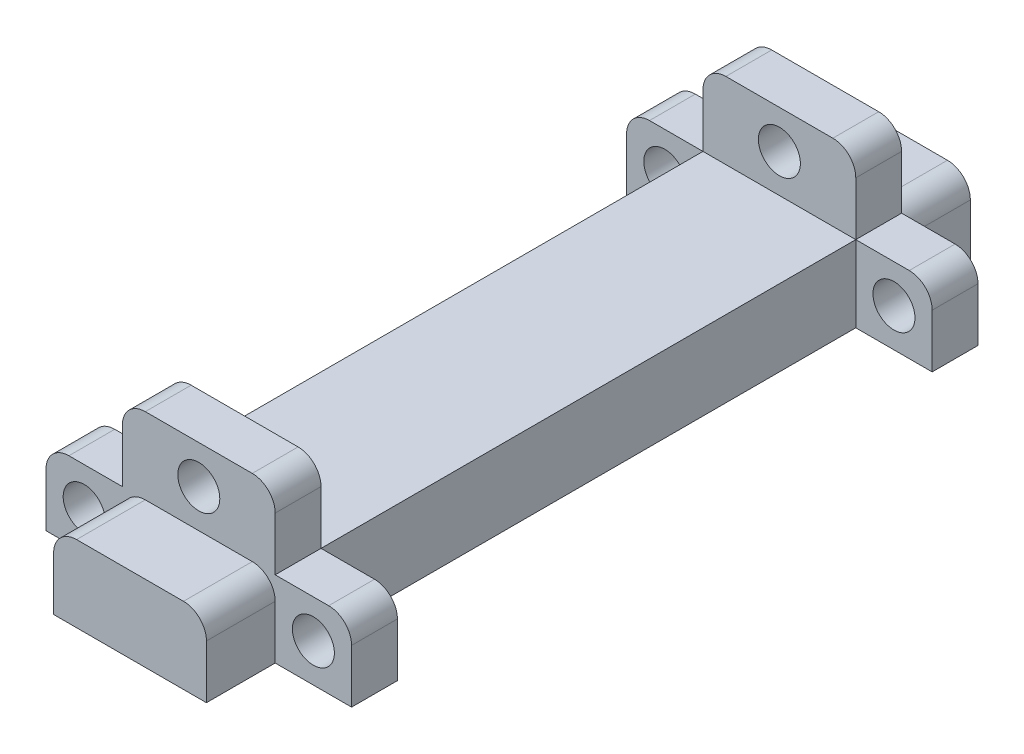
SolidWorks part; units mm, degrees
ref_plane "前视基准面" through (0, 0, 0) normal (0, 0, 1) x (1, 0, 0)
ref_plane "上视基准面" through (0, 0, 0) normal (0, 1, 0) x (1, 0, 0)
ref_plane "右视基准面" through (0, 0, 0) normal (1, 0, 0) x (0, 0, -1)
other "Configuration Table"
sketch "草图1" plane through (0, 0, 0) normal (0, 0, 1) x (1, 0, 0)
  line L1 (0, 0) -> (20, 0)
  line L2 (0, 0) -> (0, 10)
  line L3 (0, 10) -> (20, 10)
  line L4 (20, 0) -> (20, 10)
  dimension "D1" = 20
  dimension "D2" = 10
extrude "凸台-拉伸1" add sketch "草图1" along normal blind 100 contours L2 L3 L4 L1
sketch "草图2" plane through (0, 0, 0) normal (0, 0, -1) x (-1, 0, 0)
  line L1 (-20, 10) -> (0, 10)
  line L2 (-20, 10) -> (-20, 20)
  line L3 (-20, 20) -> (0, 20)
  line L4 (0, 10) -> (0, 20)
  line L5 (0, 0) -> (10, 0)
  line L6 (0, 0) -> (0, 10)
  line L7 (0, 10) -> (10, 10)
  line L8 (10, 0) -> (10, 10)
  line L9 (-20, 0) -> (-30, 0)
  line L10 (-20, 0) -> (-20, 10)
  line L11 (-20, 10) -> (-30, 10)
  line L12 (-30, 0) -> (-30, 10)
  line M12 (0, 10) -> (-20, 10)
  line M13 (-20, 10) -> (-20, 0)
  dimension "D1" = 10
  dimension "D2" = 10
ref_plane "基准面1" through (0, 0, 50) normal (0, 0, -1) x (-1, 0, 0)
extrude "凸台-拉伸2" add sketch "草图2" against normal blind 6 from offset 9 contours L12 L9 L11 M13 | L4 L3 L2 M12 | L6 L5 L8 L7 region at (10, 15, 0) region at (25, 5, 0) offset against normal yes
mirror "镜向1" about plane through (0, 0, 50) normal (0, 0, -1) of "凸台-拉伸2"
sketch "草图3" plane through (0, 0, 9) normal (0, 0, -1) x (-1, 0, 0)
  line L1 (-33.8025, 5) -> (20.2955, 5) construction
  line L2 (5, 14.7529) -> (5, -4.7529) construction
  line L3 (-25.6975, 15) -> (5.2513, 15) construction
  line L4 (-10, 22.4765) -> (-10, 13.0669) construction
  line L5 (0, 10) -> (0, 20) construction
  line L6 (-20, 10) -> (-20, 20) construction
  line L7 (-20, 20) -> (0, 20) construction
  line L8 (0, 10) -> (-20, 10) construction
  line L9 (0, 10) -> (10, 10) construction
  line L10 (0, 0) -> (10, 0) construction
  line L11 (10, 0) -> (10, 10) construction
  line L12 (0, 0) -> (0, 10) construction
  line L13 (-25, 12.0122) -> (-25, -3.7537) construction
  line L14 (-20, 0) -> (-20, 10) construction
  line L15 (-30, 0) -> (-30, 10) construction
  circle A0 centre (5, 5) radius 2.75
  circle A1 centre (-10, 15) radius 2.75
  circle A2 centre (-25, 5) radius 2.75
  dimension "D1" = 5.5
extrude "切除-拉伸1" cut sketch "草图3" against normal through all both and the other way through all
fillet "圆角1" radius 3 12 edges at (30, 10, 12) (20, 20, 12) (-10, 10, 12) (0, 20, 12) (0, 10, 4.5) (20, 10, 4.5) (-10, 10, 88) (30, 10, 88) (20, 20, 88) (0, 20, 88) (20, 10, 95.5) (0, 10, 95.5)
